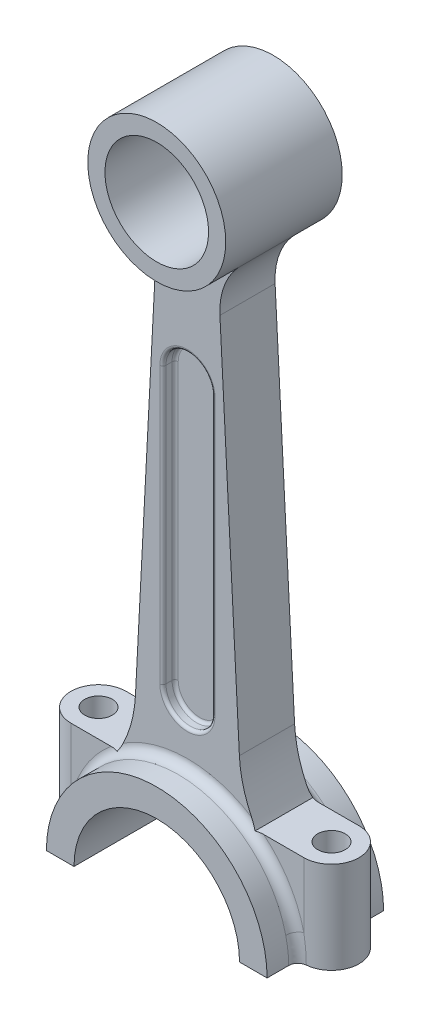
SolidWorks part; units mm, degrees
ref_plane "Front Plane" through (0, 0, 0) normal (0, 0, 1) x (1, 0, 0)
ref_plane "Top Plane" through (0, 0, 0) normal (0, 1, 0) x (1, 0, 0)
ref_plane "Right Plane" through (0, 0, 0) normal (1, 0, 0) x (0, 0, -1)
sketch "Sketch1" plane through (0, 0, 0) normal (0, 0, 1) x (1, 0, 0)
  line L0 (0, 142.0721) -> (0, -59.1279) construction
  line L1 (-10, 121.9165) -> (-17.8497, -27.8647)
  line L2 (10, 121.9165) -> (17.8497, -27.8647)
  line L3 (0, 86.4721) -> (0, -3.5279) construction
  line L6 (-36, -59.1279) -> (-27, -59.1279)
  line L7 (27, -59.1279) -> (36, -59.1279)
  line L8 (8, 86.4721) -> (8, -3.5279)
  line L9 (-8, 86.4721) -> (-8, -3.5279)
  circle A0 centre (0, 142.0721) radius 22.5
  arc A2 (-36, -59.1279) -> (36, -59.1279) centre (0, -59.1279) cw
  circle A3 centre (0, 142.0721) radius 16.9
  arc A6 (-27, -59.1279) -> (27, -59.1279) centre (0, -59.1279) cw
  arc A7 (8, 86.4721) -> (-8, 86.4721) centre (0, 86.4721) ccw
  arc A8 (-8, -3.5279) -> (8, -3.5279) centre (0, -3.5279) ccw
  point P13 (0, 41.4721)
  dimension "D1" = 45
  dimension "D2" = 36
  dimension "D5" = 33.8
  dimension "D8" = 8
  dimension "D9" = 27
  dimension "D3" = 201.2
  dimension "D4" = 6
  dimension "D6" = 20
  dimension "D7" = 90
extrude "Boss-Extrude1" add sketch "Sketch1" along normal mid plane 38 contours L6 A6 L7 A2 | A0 A3 region at (-11.5231, 160.6526, 0) region at (0, -23.9329, 0)
extrude "Boss-Extrude2" add sketch "Sketch1<3>" along normal mid plane 18 contours L1 A2 L2 A0 A8 | A8 region at (0, 118.0324, 0) region at (0, 41.4721, 0)
sketch "Sketch1<3>" plane through (0, 0, 0) normal (0, 0, 1) x (1, 0, 0) same geometry as "Sketch1"
extrude "Cut-Extrude1" cut sketch "Sketch1<4>" against normal blind 18 from offset 5 contours A7 L9 A8 L8 offset against normal yes
sketch "Sketch1<4>" plane through (0, 0, 0) normal (0, 0, 1) x (1, 0, 0) same geometry as "Sketch1"
extrude "Cut-Extrude2" cut sketch "Sketch1<6>" along normal blind 18 from offset 5 contours L8 A8 L9 A7
sketch "Sketch1<6>" plane through (0, 0, 0) normal (0, 0, 1) x (1, 0, 0) same geometry as "Sketch1"
fillet "Fillet1" radius 1 16 edges at (-8, 41.4721, -9) (0, 94.4721, -9) (8, 41.4721, -9) (-8, 41.4721, -5) (0, 94.4721, -5) (8, 41.4721, -5) (8, 41.4721, 9) (0, 94.4721, 9) (-8, 41.4721, 9) (0, 94.4721, 5) (-8, 41.4721, 5) (0, -11.5279, 5) (0, -11.5279, -9) (0, -11.5279, -5) (0, -11.5279, 9) (8, 41.4721, 5)
fillet "Fillet2" radius 40 2 edges at (17.8497, -27.8647, 0) (-17.8497, -27.8647, 0)
fillet "Fillet3" radius 22.5 2 edges at (-10, 121.9165, 0) (10, 121.9165, 0)
ref_plane "Plane1" through (0, -29.1279, 0) normal (0, 1, 0) x (1, 0, 0)
sketch "Sketch5" plane through (0, -29.1279, 0) normal (0, 1, 0) x (1, 0, 0)
  line L0 (-38, 0) -> (38, 0) construction
  line L1 (-38, 9) -> (38, 9)
  line L2 (-38, -9) -> (38, -9)
  arc A0 (-38, 9) -> (-38, -9) centre (-38, 0) ccw
  arc A1 (38, -9) -> (38, 9) centre (38, 0) ccw
  point P2 (0, 0)
  dimension "D2" = 9
  dimension "D1" = 76
extrude "Boss-Extrude3" add sketch "Sketch5" against normal up to surface (30 mm away) up to face at (-31.5, -59.1279, 0)
sketch "Sketch6" plane through (0, 0, 9) normal (0, 0, 1) x (1, 0, 0)
  line L1 (-27, -59.1279) -> (27, -59.1279)
  line L2 (-27, -59.1279) -> (27, -59.1279)
  arc A1 (27, -59.1279) -> (-27, -59.1279) centre (0, -59.1279) ccw
  arc A2 (27, -59.1279) -> (-27, -59.1279) centre (0, -59.1279) ccw
  dimension "D1" = 0
extrude "Cut-Extrude3" cut sketch "Sketch6" against normal through all
sketch "Sketch7" plane through (0, -29.1279, 0) normal (0, 1, 0) x (1, 0, 0)
  line L0 (0, -20.9) -> (0, 20.9) construction
  circle A1 centre (38, 0) radius 4.5
  circle A2 centre (-38, 0) radius 4.5
  dimension "D1" = 9
extrude "Cut-Extrude4" cut sketch "Sketch7" against normal through all
fillet "Fillet4" radius 3 2 edges at (0, -23.1279, -9) (0, -23.1279, 9)
